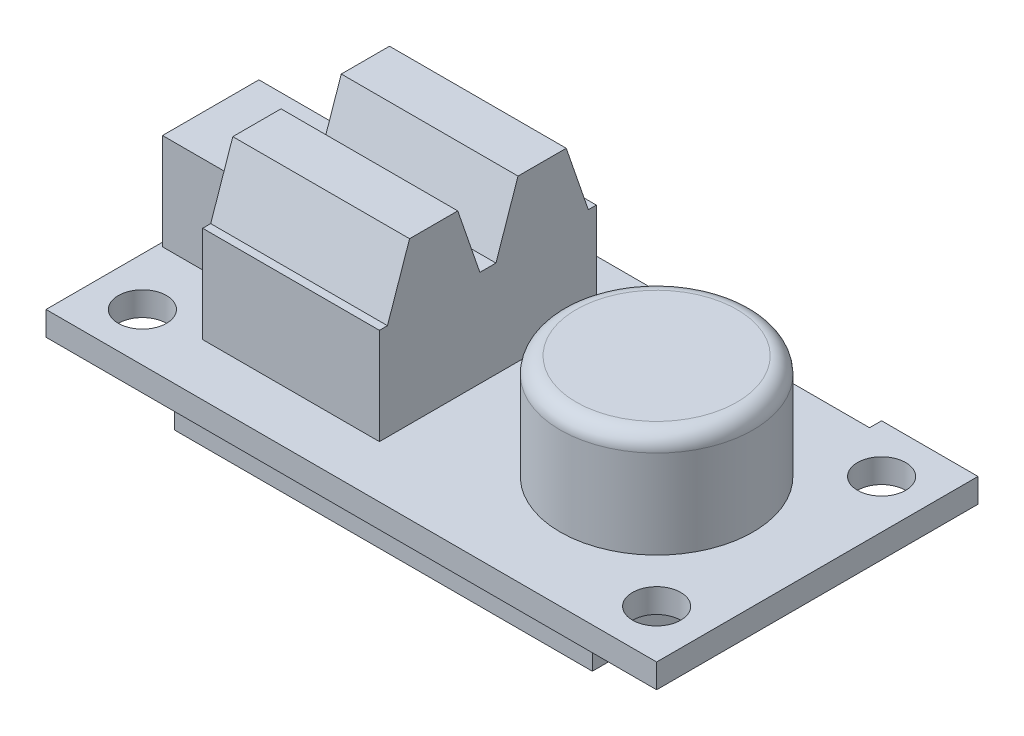
SolidWorks part; units mm, degrees
ref_plane "Front Plane" through (0, 0, 0) normal (0, 0, 1) x (1, 0, 0)
ref_plane "Top Plane" through (0, 0, 0) normal (0, 1, 0) x (1, 0, 0)
ref_plane "Right Plane" through (0, 0, 0) normal (1, 0, 0) x (0, 0, -1)
sketch "Sketch1" plane through (0, 0, 0) normal (0, 1, 0) x (1, 0, 0)
  line L0 (-16, 7) -> (16, 7) construction
  line L1 (-19, -10) -> (19, -10)
  line L2 (-19, -10) -> (-19, 10)
  line L3 (-19, 10) -> (1, 10)
  line L4 (19, -10) -> (19, 10)
  line L5 (-19, -10) -> (19, 10) construction
  line L6 (-19, 10) -> (19, -10) construction
  line L7 (16, 7) -> (16, -7) construction
  line L8 (16, -7) -> (-16, -7) construction
  line L9 (-16, -7) -> (-16, 7) construction
  line L10 (13, 10) -> (13, 9.25)
  line L11 (13, 9.25) -> (1, 9.25)
  line L12 (1, 9.25) -> (1, 10)
  line L13 (1, 10) -> (13, 10) construction
  line L14 (13, 10) -> (19, 10)
  circle A0 centre (-16, 7) radius 1.5
  circle A1 centre (-16, -7) radius 1.5
  circle A2 centre (16, -7) radius 1.5
  circle A3 centre (16, 7) radius 1.5
  point P0 (0, 0)
  point P14 (0, 7)
  point P15 (0, -7)
  point P16 (-16, 0)
  point P17 (16, 0)
  dimension "D3" = 3
  dimension "D1" = 20
  dimension "D2" = 38
  dimension "D4" = 3
  dimension "D5" = 3
  dimension "D6" = 6
  dimension "D7" = 12
  dimension "D8" = 0.75
extrude "Boss-Extrude1" add sketch "Sketch1" along normal blind 1.5
sketch "Sketch2" plane through (0, 1.5, 0) normal (0, 1, 0) x (1, 0, 0)
  line L0 (19, -10) -> (19, 10) construction
  circle A0 centre (9, 0) radius 6
  dimension "D2" = 12
  dimension "D1" = 10
extrude "Boss-Extrude2" add sketch "Sketch2" along normal blind 6.5
fillet "Fillet1" radius 1 1 edges at (9, 8, 6)
sketch "Sketch3" plane through (0, 1.5, 0) normal (0, 1, 0) x (1, 0, 0)
  line L1 (-18.75, 3) -> (-13.75, 3)
  line L2 (-18.75, 3) -> (-18.75, -3)
  line L3 (-18.75, -3) -> (-13.75, -3)
  line L4 (-13.75, 3) -> (-13.75, -3)
  line L5 (-18.75, 3) -> (-13.75, -3) construction
  line L6 (-18.75, -3) -> (-13.75, 3) construction
  line L7 (-4.4, 0) -> (4.4, 0) construction
  line L8 (-19, 10) -> (-19, -10) construction
  point P0 (-16.25, 0)
  dimension "D1" = 5
  dimension "D2" = 6
  dimension "D3" = 0.25
extrude "Boss-Extrude3" add sketch "Sketch3" along normal blind 6
sketch "Sketch5" plane through (0, 0, 0) normal (1, 0, 0) x (0, 0, -1)
  line L0 (6.75, 1.5) -> (6.75, 7.5)
  line L1 (0, 7.5) -> (0, 1.5) construction
  line L2 (6.75, 7.5) -> (6.25, 7.5)
  line L3 (6.25, 7.5) -> (4.875, 11.5)
  line L4 (4.875, 11.5) -> (1.875, 11.5)
  line L5 (1.875, 11.5) -> (0.5, 7.5)
  line L6 (0.5, 7.5) -> (-0.5, 7.5)
  line L7 (-0.5, 7.5) -> (-1.875, 11.5)
  line L8 (-1.875, 11.5) -> (-4.875, 11.5)
  line L9 (-4.875, 11.5) -> (-6.25, 7.5)
  line L10 (-6.25, 7.5) -> (-6.75, 7.5)
  line L11 (-6.75, 7.5) -> (-6.75, 1.5)
  line L12 (-6.75, 1.5) -> (6.75, 1.5)
  line L13 (10, 1.5) -> (-10, 1.5) construction
  line L15 (-1.875, 11.5) -> (1.875, 11.5) construction
  point P2 (0, 11.5)
  point P4 (0, 7.5)
  point P16 (0, 1.5)
  dimension "D1" = 3
  dimension "D2" = 13.5
  dimension "D3" = 0.5
  dimension "D4" = 0.5
  dimension "D5" = 1
  dimension "D6" = 6
  dimension "D7" = 4
extrude "Boss-Extrude4" add sketch "Sketch5" along normal blind 11 from offset 12.5 offset against normal yes
sketch "Sketch6" plane through (0, 0, 0) normal (0, -1, 0) x (1, 0, 0)
  line L1 (-13, -8) -> (13, -8)
  line L2 (-13, -8) -> (-13, 8)
  line L3 (-13, 8) -> (13, 8)
  line L4 (13, -8) -> (13, 8)
  line L5 (-13, -8) -> (13, 8) construction
  line L6 (-13, 8) -> (13, -8) construction
  point P0 (0, 0)
  dimension "D1" = 16
  dimension "D2" = 26
extrude "Boss-Extrude5" add sketch "Sketch6" along normal blind 3
